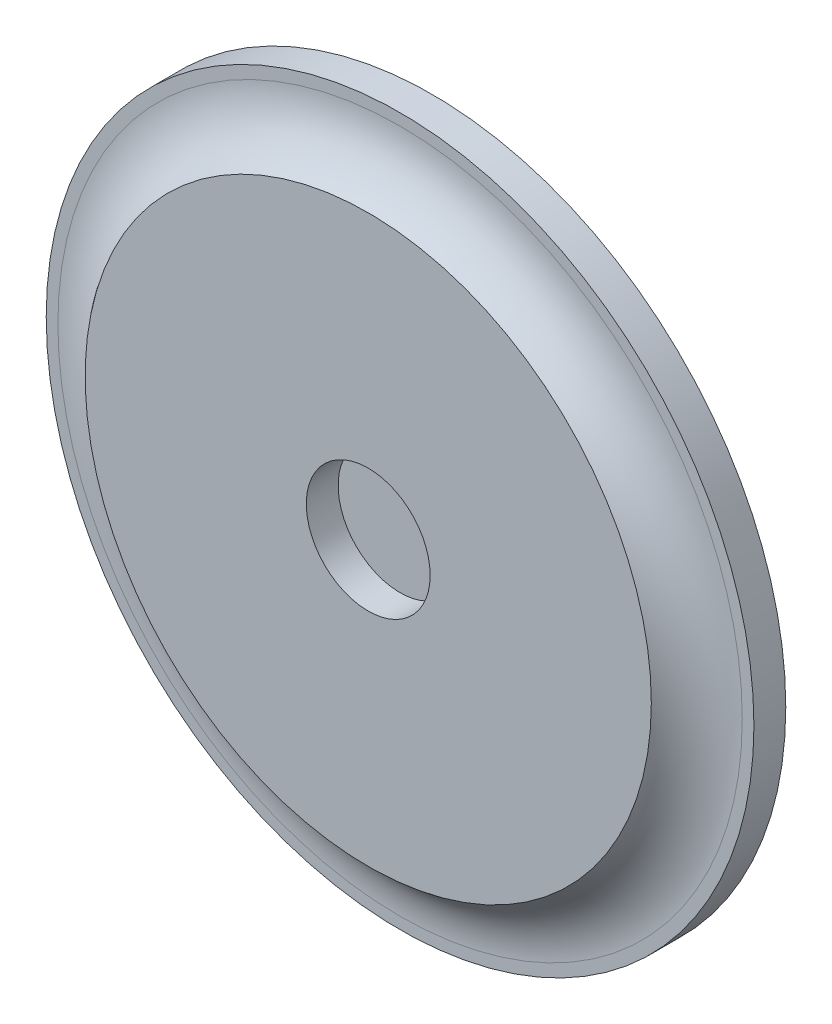
SolidWorks part; units mm, degrees
ref_plane "Front Plane" through (0, 0, 0) normal (1, 0, 0) x (0, 1, 0)
ref_plane "Top Plane" through (0, 0, 0) normal (0, 0, 1) x (0, 1, 0)
ref_plane "Right Plane" through (0, 0, 0) normal (0, 1, 0) x (-1, 0, 0)
sketch "Sketch1" plane through (0, 0, 0) normal (0, 0, 1) x (0, 1, 0)
  circle A0 centre (0, 0) radius 10
  dimension "D1" = 20
extrude "Boss-Extrude1" add sketch "Sketch1" along normal blind 1.8
sketch "Sketch2" plane through (0, 0, 1.8) normal (0, 0, 1) x (1, 0, 0)
  circle A0 centre (0, 0) radius 10
  circle A1 centre (0, 0) radius 8
  dimension "D1" = 16
extrude "Cut-Extrude1" cut sketch "Sketch2" against normal blind 0.9
fillet "Fillet2" radius 2 1 edges at (8, 0, 0.9)
sketch "Sketch3" plane through (0, 0, 1.8) normal (0, 0, 1) x (1, 0, 0)
  circle A0 centre (0, 0) radius 1.75
  dimension "D1" = 3.5
extrude "Cut-Extrude2" cut sketch "Sketch3" against normal blind 0.9
